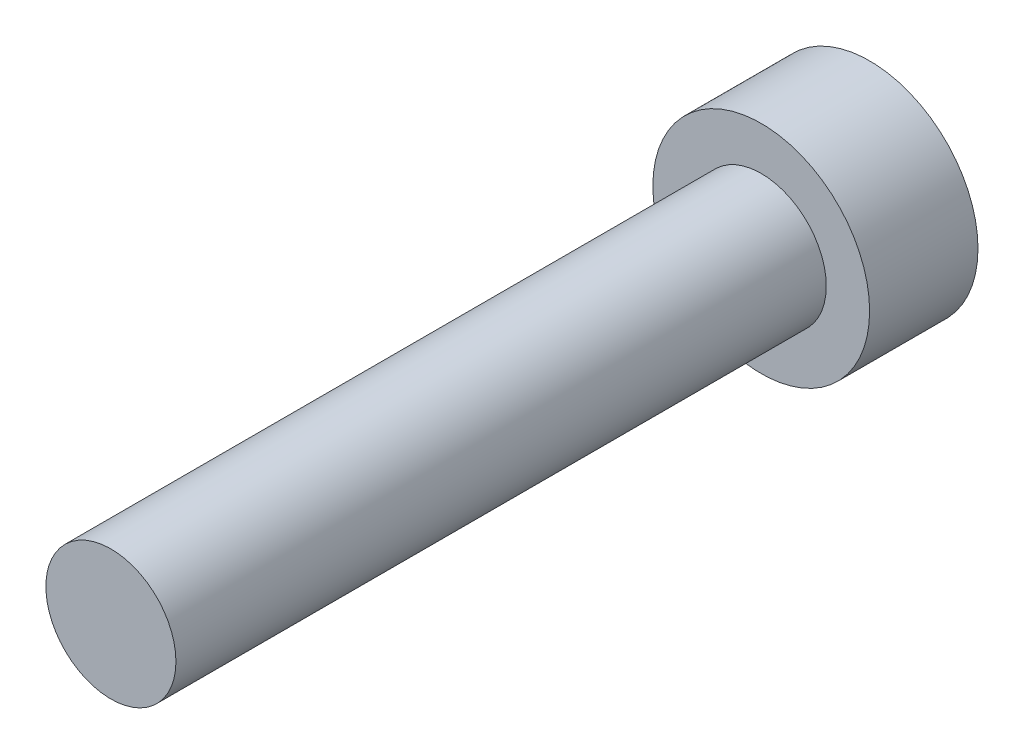
SolidWorks part; units mm, degrees
material "Chrome Stainless Steel"
ref_plane "Front Plane" through (0, 0, 0) normal (0, 0, 1) x (1, 0, 0)
ref_plane "Top Plane" through (0, 0, 0) normal (0, 1, 0) x (1, 0, 0)
ref_plane "Right Plane" through (0, 0, 0) normal (1, 0, 0) x (0, 0, -1)
sketch "Sketch1" plane through (0, 0, 0) normal (0, 0, 1) x (1, 0, 0)
  circle A0 centre (0, 0) radius 2.5
  circle A1 centre (0, 0) radius 1.5
  dimension "D1" = 5
  dimension "D2" = 3
extrude "Boss-Extrude3" add sketch "Sketch1" against normal blind 2.5 contours A0 A1 | A1 region at (-2.4293, 0, 0) region at (0, 0, 0)
extrude "Boss-Extrude4" add sketch "Sketch1<3>" along normal blind 15 contours A1 region at (0, 0, 0)
sketch "Sketch1<3>" plane through (0, 0, 0) normal (0, 0, 1) x (1, 0, 0) same geometry as "Sketch1"
